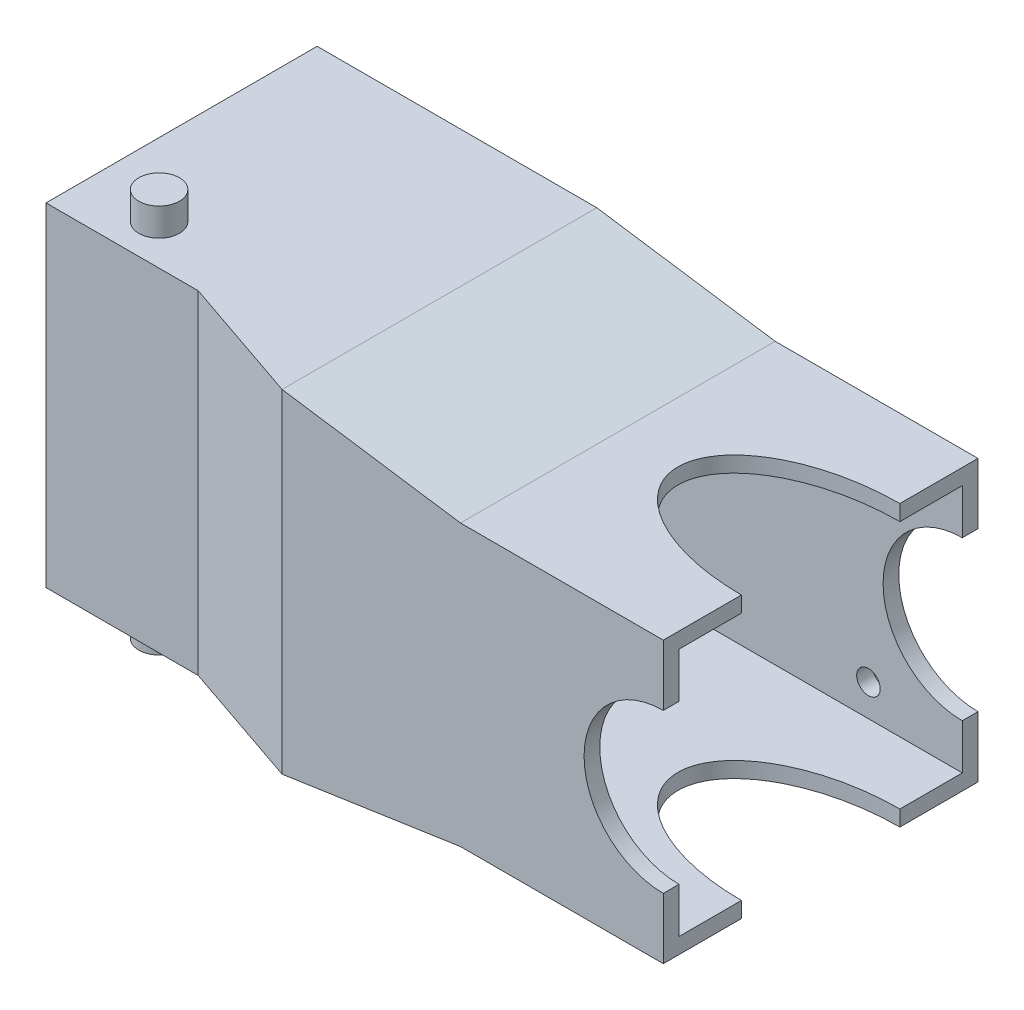
SolidWorks part; units mm, degrees
ref_plane "Plan de face" through (0, 0, 0) normal (0, 0, 1) x (1, 0, 0)
ref_plane "Plan de dessus" through (0, 0, 0) normal (0, 1, 0) x (1, 0, 0)
ref_plane "Plan de droite" through (0, 0, 0) normal (1, 0, 0) x (0, 0, -1)
sketch "Esquisse1" plane through (0, 0, 0) normal (1, 0, 0) x (0, 0, -1)
  line L1 (22.05, -19.635) -> (-22.05, -19.635)
  line L2 (22.05, -19.635) -> (22.05, 19.635)
  line L3 (22.05, 19.635) -> (-22.05, 19.635)
  line L4 (-22.05, -19.635) -> (-22.05, 19.635)
  line L5 (22.05, -19.635) -> (-22.05, 19.635) construction
  line L6 (22.05, 19.635) -> (-22.05, -19.635) construction
  point P0 (0, 0)
  dimension "D1" = 39.27
  dimension "D2" = 44.1
extrude "Boss.-Extru.1" add sketch "Esquisse1" along normal blind 28.42
sketch "Esquisse2" plane through (0, 0, 0) normal (-1, 0, 0) x (0, 0, 1)
  line L0 (22.05, 19.635) -> (22.05, -19.635) construction
  line L1 (-19.85, 17.435) -> (19.85, 17.435)
  line L2 (-19.85, 17.435) -> (-19.85, -17.435)
  line L3 (-19.85, -17.435) -> (19.85, -17.435)
  line L4 (19.85, 17.435) -> (19.85, -17.435)
  line L5 (-19.85, 17.435) -> (19.85, -17.435) construction
  line L6 (-19.85, -17.435) -> (19.85, 17.435) construction
  line L7 (-22.05, 19.635) -> (22.05, 19.635) construction
  point P0 (0, 0)
  dimension "D1" = 2.2
  dimension "D2" = 2.2
extrude "Enlèv. mat.-Extru.1" cut sketch "Esquisse2" against normal blind 28.42
sketch "Esquisse3" plane through (0, 0, 22.05) normal (0, 0, 1) x (1, 0, 0)
  line L0 (28.42, 19.635) -> (28.42, -19.635) construction
  circle A0 centre (28.42, 0) radius 11.1
extrude "Enlèv. mat.-Extru.2" cut sketch "Esquisse3" against normal blind 50
sketch "Esquisse4" plane through (0, -19.635, 0) normal (0, -1, 0) x (1, 0, 0)
  line L0 (28.42, 22.05) -> (28.42, -22.05) construction
  ellipse E0 centre (28.42, 0) end of major axis (8.42, 0) minor radius 11.1
extrude "Enlèv. mat.-Extru.3" cut sketch "Esquisse4" against normal blind 50
sketch "Esquisse5" plane through (0, 0, -22.05) normal (0, 0, -1) x (-1, 0, 0)
  line L0 (-28.42, -19.635) -> (-28.42, -11.1) construction
  line L2 (-28.42, -19.635) -> (0, -19.635) construction
  line L3 (0, 0) -> (-17.32, 0) construction
  circle A0 centre (-15.27, -12.985) radius 1.65
  arc A1 (-28.42, -11.1) -> (-28.42, 11.1) centre (-28.42, 0) ccw construction
  circle A2 centre (-15.27, 12.985) radius 1.65
  point P4 (-28.42, -15.3675)
  point P7 (-14.21, -19.635)
  point P16 (0, 0)
  dimension "D1" = 13.15
  dimension "D2" = 6.65
extrude "Enlèv. mat.-Extru.4" cut sketch "Esquisse5" against normal blind 10
sketch "Esquisse6" plane through (0, 0, -22.05) normal (0, 0, -1) x (-1, 0, 0)
  line L0 (0, 19.635) -> (0, -19.635)
  line L1 (0, 19.635) -> (64.18, 19.635)
  line L2 (0, -19.635) -> (64.18, -19.635)
  line L3 (64.18, 19.635) -> (64.18, -19.635)
  dimension "D1" = 64.18
extrude "Boss.-Extru.2" add sketch "Esquisse6" against normal blind 2.2
sketch "Esquisse7" plane through (0, 0, -22.05) normal (0, 0, -1) x (-1, 0, 0)
  line L0 (0, 0) -> (64.18, 0) construction
  line L1 (64.18, -19.635) -> (64.18, 19.635) construction
sketch "Esquisse8" plane through (0, 0, 0) normal (-1, 0, 0) x (0, 0, 1)
  line L0 (22.05, -19.635) -> (-22.05, -19.635)
  line L1 (22.05, -19.635) -> (22.05, 19.635)
  line L2 (-22.05, -19.635) -> (-22.05, 19.635)
  line L3 (22.05, 19.635) -> (-22.05, 19.635)
extrude "Boss.-Extru.3" add sketch "Esquisse8" along normal blind 25
sketch "Esquisse10" plane through (0, 0, 22.05) normal (0, 0, 1) x (1, 0, 0)
  line L0 (-25, -19.635) -> (0, -19.635)
  line L1 (28.42, -19.635) -> (-25, -19.635) construction
  line L2 (0, -19.635) -> (-25, -23.345)
  line L3 (-25, -23.345) -> (-25, -19.635)
  line L4 (-25, 0) -> (0, 0) construction
  line L5 (-25, -19.635) -> (-25, 19.635) construction
  line L6 (-25, 19.635) -> (0, 19.635)
  line L7 (-25, 23.345) -> (-25, 19.635)
  line L8 (0, 19.635) -> (-25, 23.345)
  dimension "D1" = 3.71
extrude "Boss.-Extru.4" add sketch "Esquisse10" against normal up to vertex (44.1 mm away) up to point (28.42, -19.635, -22.05)
sketch "Esquisse13" plane through (0, 0, -22.05) normal (0, 0, -1) x (-1, 0, 0)
  line L0 (64.18, 19.635) -> (25, 19.635)
  line L1 (64.18, 19.635) -> (64.18, 23.345)
  line L2 (25, 19.635) -> (25, 23.345)
  line L3 (64.18, 23.345) -> (25, 23.345)
  line L4 (25, -23.345) -> (25, -19.635)
  line L5 (25, -23.345) -> (64.18, -23.345)
  line L6 (25, -19.635) -> (64.18, -19.635)
  line L7 (64.18, -23.345) -> (64.18, -19.635)
extrude "Boss.-Extru.5" add sketch "Esquisse13" against normal up to vertex (2.2 mm away) up to point (-25, 19.635, -19.85)
sketch "Esquisse14" plane through (0, 0, 0) normal (1, 0, 0) x (0, 0, -1)
  line L0 (-19.85, 17.435) -> (19.85, 17.435)
  line L1 (-19.85, 17.435) -> (-19.85, -17.435)
  line L2 (19.85, 17.435) -> (19.85, -17.435)
  line L3 (-19.85, -17.435) -> (19.85, -17.435)
  point P0 (19.85, -17.435)
extrude "Enlèv. mat.-Extru.5" cut sketch "Esquisse14" against normal blind 25
sketch "Esquisse17" plane through (-64.18, 0, 0) normal (-1, 0, 0) x (0, 0, 1)
  line L0 (-22.05, 23.345) -> (-22.05, -23.345)
  line L1 (-22.05, 23.345) -> (15.95, 23.345)
  line L2 (-22.05, -23.345) -> (15.95, -23.345)
  line L3 (15.95, 23.345) -> (15.95, -23.345)
  dimension "D1" = 46.69
  dimension "D2" = 38
extrude "Boss.-Extru.6" add sketch "Esquisse17" against normal up to vertex (39.18 mm away) up to point (-25, 23.345, 22.05)
sketch "Esquisse18" plane through (-64.18, 0, 0) normal (-1, 0, 0) x (0, 0, 1)
  line L0 (-21.4975, 21.145) -> (13.75, 21.145)
  line L1 (-21.4975, 21.145) -> (-21.4975, -21.145)
  line L2 (13.75, 21.145) -> (13.75, -21.145)
  line L3 (-21.4975, -21.145) -> (13.75, -21.145)
  line L4 (15.95, 23.345) -> (-22.05, 23.345) construction
  line L5 (15.95, -23.345) -> (-22.05, -23.345) construction
  line L6 (15.95, -23.345) -> (15.95, 23.345) construction
  point P6 (-3.8738, 21.145)
  point P9 (13.75, 0)
  dimension "D1" = 2.2
  dimension "D2" = 2.2
  dimension "D3" = 2.2
extrude "Enlèv. mat.-Extru.6" cut sketch "Esquisse18" against normal blind 50
ref_plane "Plan7" through (-25, -17.435, 15.95) normal (0, 1, 0) x (1, 0, 0)
sketch "Esquisse21" plane through (0, 0, 22.05) normal (0, 0, 1) x (1, 0, 0)
sketch "Esquisse22" plane through (0, -23.345, 0) normal (0, -1, 0) x (1, 0, 0)
  line L0 (-42.8457, 15.95) -> (-25, 15.95)
  line L1 (-25, 15.95) -> (-25, 22.05)
  line L2 (-25, 22.05) -> (-42.8457, 15.95)
  point P7 (0, 0)
  point P8 (0, 0)
  point P9 (-42.8457, 15.95)
extrude "Boss.-Extru.7" add sketch "Esquisse22" against normal up to vertex (46.69 mm away) up to point (-25, 23.345, 15.95)
fillet "Congé1" radius 50 1 edges at (-25, 0, 13.75)
sketch "Esquisse23" plane through (0, 23.345, 0) normal (0, 1, 0) x (1, 0, 0)
  line L0 (-64.18, -15.95) -> (-64.18, 22.05) construction
  line L1 (-42.8457, -15.95) -> (-64.18, -15.95) construction
  circle A0 centre (-53.98, -10.3) radius 2.85
  dimension "D1" = 10.2
  dimension "D2" = 5.65
extrude "Boss.-Extru.8" add sketch "Esquisse23" along normal blind 3.9
sketch "Esquisse24" plane through (0, 0, 15.95) normal (0, 0, 1) x (1, 0, 0)
  line L0 (-64.18, 0) -> (-42.8457, 0) construction
  line L1 (-64.18, -23.345) -> (-64.18, 23.345) construction
  line L2 (-42.8457, 23.345) -> (-42.8457, -23.345) construction
sketch "Esquisse26" plane through (0, -23.345, 0) normal (0, -1, 0) x (1, 0, 0)
  line L0 (-42.8457, 15.95) -> (-64.18, 15.95) construction
  line L1 (-64.18, 15.95) -> (-64.18, -22.05) construction
  circle A0 centre (-53.98, 10.3) radius 2.85
  dimension "D1" = 5.65
  dimension "D2" = 10.2
extrude "Boss.-Extru.9" add sketch "Esquisse26" along normal blind 3.9
equation "\"2.27.00mm\"=10"
